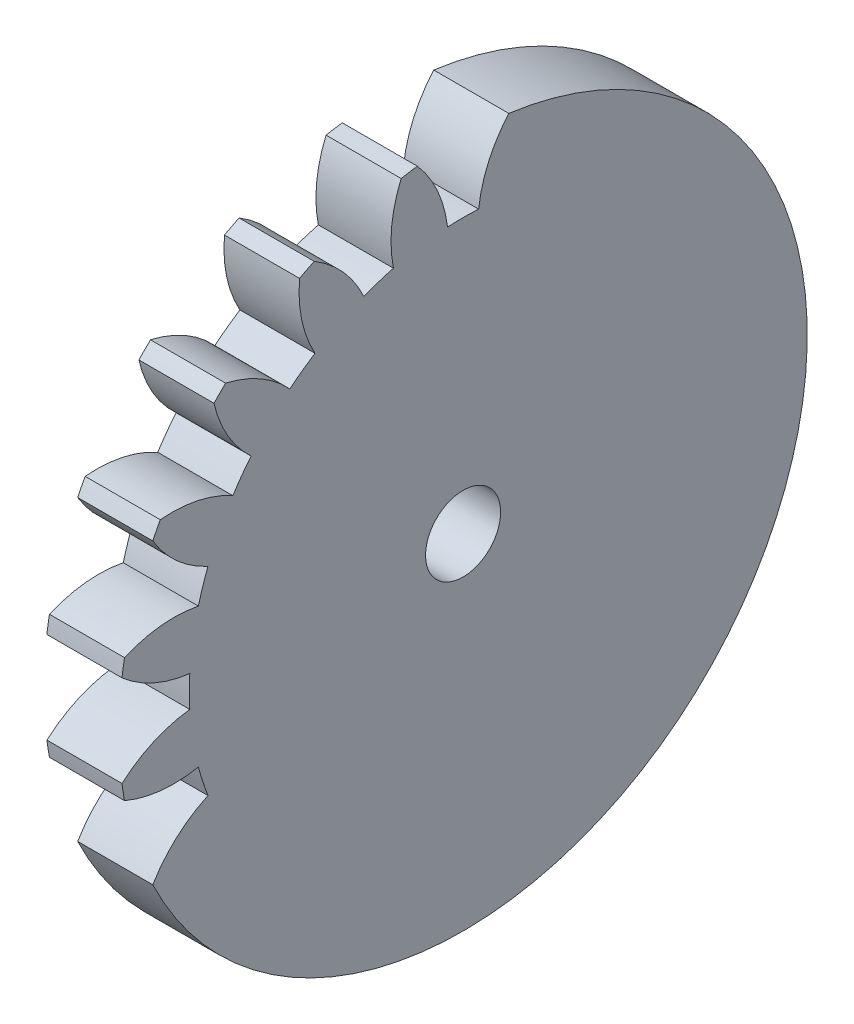
SolidWorks part; units mm, degrees
ref_plane "Plane1" through (0, 0, 0) normal (0, 0, 1) x (1, 0, 0)
ref_plane "Plane2" through (0, 0, 0) normal (0, 1, 0) x (1, 0, 0)
ref_plane "Plane3" through (0, 0, 0) normal (1, 0, 0) x (0, 0, -1)
sketch "HoldingSke" plane through (0, 0, 0) normal (0, 1, 0) x (1, 0, 0)
  line L0 (0, 0) -> (0.7518, -0.2736)
  line L1 (-15, 0) -> (100, 0) construction
  line L2 (0, 0) -> (-2.1039, 2.3779)
  line L3 (0, 0) -> (-11.863, 4.5341)
  line L4 (0, 0) -> (8.1152, 2.9537)
  line L5 (0, 0) -> (-46.8476, -17.4728)
  line L6 (0, 0) -> (-9.9476, -6.7116)
  line L7 (-2.1039, 2.3779) -> (8.6586, 51.2059)
  line L8 (-76.2, 54.61) -> (-75.7, 54.61)
  line L9 (-71.009, 38.7566) -> (-53.1078, 45.2721)
  line L10 (-76.2, 71.12) -> (104.1128, 71.12)
  line L11 (0, 0) -> (-12, 0)
  line L12 (-76.2, 101.6) -> (-76.155, 101.6)
  line L13 (24.9733, 27.94) -> (52.9518, 28.4284)
  line L14 (24.9733, 27.94) -> (24.9743, 27.94)
  line L15 (24.9733, 27.94) -> (100.4006, 29.5858)
  line L16 (-63.627, -1.25) -> (-12.827, -1.25)
  circle A0 centre (0, 0) radius 1.5
  circle A1 centre (0, 0) radius 10.9365
  circle A2 centre (0, 0) radius 37.5
  circle A3 centre (0, 0) radius 1.5
  dimension "Num_teeth" = 20
  dimension "Pitch_radius" = 180.3128
  dimension "Width" = 12
sketch "BasProSke" plane through (0, 0, 0) normal (0, 1, 0) x (1, 0, 0)
  line L0 (-10, 0) -> (60, 0) construction
  line L1 (0, 0) -> (0, 13.75)
  line L2 (0, 0) -> (3, 0)
  line L3 (3, 0) -> (3, 13.75)
  line L4 (3, 13.75) -> (0, 13.75)
  dimension "Thickness" = 3
  dimension "Diameter" = 27.5
revolve "Base-Revolve" add sketch "BasProSke" angle 360 about L0
sketch "TooCutSke" plane through (0, 0, 0) normal (1, 0, 0) x (0, 0, -1)
  line L1 (0, 0) -> (0, 107) construction
  line L2 (0, 0) -> (-1.0594, 12.455) construction
  line L3 (0, 0) -> (-3.9007, 24.6278) construction
  line L4 (-1.0594, 12.455) -> (-1.9503, 12.3139) construction
  arc A0 (0.6211, 10.9188) -> (-0.6211, 10.9188) centre (0, 0) ccw
  arc A1 (1.8466, 13.6511) -> (-1.8466, 13.6511) centre (0, 0) ccw
  circle A2 centre (0, 0) radius 12.5 construction
  circle A3 centre (0, 0) radius 11.7462 construction
  arc A4 (-0.6211, 10.9188) -> (-1.8466, 13.6511) centre (-5.5866, 10.3326) ccw
  arc A5 (1.8466, 13.6511) -> (0.6211, 10.9188) centre (5.5866, 10.3326) ccw
extrude "ToothCut" cut sketch "TooCutSke" along normal through all
fillet "Breaks" [suppressed] radius 0.025 tangent propagation no
fillet "RootFillets" [suppressed] radius 0.3135
pattern_circular "TeethCuts" count 7 every 18 about axis through (-10, 0, 0) along (1, 0, 0) of "ToothCut"
sketch "HubNeaOneSke" plane through (0, 0, 0) normal (-1, 0, 0) x (0, 0, 1)
  circle A0 centre (0, 0) radius 10.9365
  dimension "Diameter" = 21.873
extrude "HubNearOne" [suppressed] add sketch "HubNeaOneSke" along normal blind 47.0001
sketch "HubNeaBotSke" plane through (0, 0, 0) normal (-1, 0, 0) x (0, 0, 1)
  circle A0 centre (0, 0) radius 10.9365
  dimension "Diameter" = 21.873
extrude "HubNearBoth" [suppressed] add sketch "HubNeaBotSke" along normal blind 23.5
ref_plane "FarPln" through (3, 0, 0) normal (1, 0, 0) x (0, 0, -1)
sketch "HubFarSke" plane through (3, 0, 0) normal (1, 0, 0) x (0, 0, -1)
  circle A0 centre (0, 0) radius 10.9365
  dimension "Diameter" = 21.873
extrude "HubFar" [suppressed] add sketch "HubFarSke" along normal blind 23.5
sketch "BorSke" plane through (0, 0, 0) normal (1, 0, 0) x (0, 0, -1)
  circle A0 centre (0, 0) radius 1.5
  dimension "Diameter" = 3
extrude "Bore" cut sketch "BorSke" along normal mid plane 100.0001
sketch "KeySke" plane through (0, 0, 0) normal (1, 0, 0) x (0, 0, -1)
  line L0 (-0.6, 0) -> (-0.6, 2)
  line L1 (-0.6, 2) -> (0.6, 2)
  line L2 (0.6, 2) -> (0.6, 0)
  line L3 (0, 0) -> (0, 34) construction
  line L4 (-0.6, 0) -> (0.6, 0)
extrude "Keyway" [suppressed] cut sketch "KeySke" along normal mid plane 100.0001
equation "' \"Module@HoldingSke\" = 6.35"
equation "' \"Num_teeth@HoldingSke\" = 12"
equation "' \"Ap@HoldingSke\" =  20"
equation "' \"Ap@HoldingSke\" = 20"
equation "' \"Width@HoldingSke\" = 0.5 * 25.4"
equation "' \"Hub_dia@HoldingSke\"= 1 * 25.4"
equation "' \"Hub_dia@HoldingSke\" = 1 * 25.4"
equation "' \"Overall_len@HoldingSke\" = 1.0 * 25.4"
equation "' \"Bore@HoldingSke\" = 0.75 * 25.4"
equation "' \"T_dim@HoldingSke\" = 0.1 * 25.4"
equation "' \"Width@KeySke\" = 0.25 * 25.4"
equation "' \"Show_teeth@HoldingSke\" = 13"
equation "' \"Backlash@HoldingSke\" = 0.009 * 25.4"
equation "' \"Addendum_fac@HoldingSke\" = 1.0"
equation "' \"Dedendum_fac@HoldingSke\" = 1.25"
equation "' \"Dedendum_add@HoldingSke\" = 0.00005 * 25.4"
equation "' \"Clearance_fac@HoldingSke\" = 0.25"
equation "\"Pitch@HoldingSke\" = 1 / \"Module@HoldingSke\""
equation "\"Overcut_dia@TooCutSke\" = (\"Num_teeth@HoldingSke\" + 2 * \"Addendum_fac@HoldingSke\") / \"Pitch@HoldingSke\" + 0.002 * 25.4"
equation "\"Pitch_dia@TooCutSke\" = \"Num_teeth@HoldingSke\" / \"Pitch@HoldingSke\""
equation "\"Base_dia@TooCutSke\" = \"Num_teeth@HoldingSke\" / \"Pitch@HoldingSke\" * cos((\"Ap@HoldingSke\"  * 3.14159265 / 180))"
equation "\"Root_dia@TooCutSke\" = (\"Num_teeth@HoldingSke\" + 2) / \"Pitch@HoldingSke\" - 2 * (\"Addendum_fac@HoldingSke\" + \"Dedendum_fac@HoldingSke\") / \"Pitch@HoldingSke\" - \"Dedendum_add@HoldingSke\" * 2"
equation "\"Half_ang@TooCutSke\" = 180 / \"Num_teeth@HoldingSke\""
equation "\"Half_CT@TooCutSke\" = \"Num_teeth@HoldingSke\" / \"Pitch@HoldingSke\" * sin((3.14159265 / 2 / \"Num_teeth@HoldingSke\")) / 2 - 7 * \"Backlash@HoldingSke\" / 4"
equation "\"Flank_rad@TooCutSke\" = \"Num_teeth@HoldingSke\" / \"Pitch@HoldingSke\" / 5"
equation "\"Radius@RootFillets\" = \"Clearance_fac@HoldingSke\" / \"Pitch@HoldingSke\" + \"Dedendum_add@HoldingSke\""
equation "\"Break_rad@Breaks\" = 0.02 / \"Pitch@HoldingSke\""
equation "\"Thickness@HoldingSke\" = \"Width@HoldingSke\""
equation "\"OAL@HoldingSke\" = \"Thickness@HoldingSke\""
equation "\"MHD@HoldingSke\" = (\"Num_teeth@HoldingSke\" + 2) / \"Pitch@HoldingSke\" - 2 * (\"Addendum_fac@HoldingSke\" + \"Dedendum_fac@HoldingSke\")  / \"Pitch@HoldingSke\" - \"Dedendum_add@HoldingSke\" * 2"
equation "\"MBD@HoldingSke\" = (\"Num_teeth@HoldingSke\" + 2) / \"Pitch@HoldingSke\" - 2 * (\"Addendum_fac@HoldingSke\" + \"Dedendum_fac@HoldingSke\")  / \"Pitch@HoldingSke\" - \"Dedendum_add@HoldingSke\" * 2 - 0.002 * 25.4"
equation "\"MHD@HoldingSke\" = ((sgn( \"MHD@HoldingSke\" - \"Hub_dia@HoldingSke\" )-1)*( \"MHD@HoldingSke\" - \"Hub_dia@HoldingSke\" ))/-2+ \"Hub_dia@HoldingSke\""
equation "\"MBD@HoldingSke\" = ((sgn( \"MBD@HoldingSke\" - \"Bore@HoldingSke\" )-1)*( \"MBD@HoldingSke\" - \"Bore@HoldingSke\" ))/-2+ \"Bore@HoldingSke\""
equation "\"OAL@HoldingSke\" = ((sgn( \"OAL@HoldingSke\" - \"Overall_len@HoldingSke\" )+1)*( \"OAL@HoldingSke\" - \"Overall_len@HoldingSke\" ))/2 + \"Overall_len@HoldingSke\" + 0.000002 * 25.4"
equation "\"Num_teeth@TeethCuts\" = ((sgn( \"Num_teeth@TeethCuts\" - 2.0)+1)*( \"Num_teeth@TeethCuts\" - 2.0))/2 +2.0"
equation "\"Diameter@BasProSke\" = (\"Num_teeth@HoldingSke\" + 2 * \"Addendum_fac@HoldingSke\") / \"Pitch@HoldingSke\""
equation "' \"Fillet_rad@BasProSke\" =  \"Thickness@HoldingSke\" * 0.05"
equation "' \"Fillet_rad@BasProSke\" = \"Thickness@HoldingSke\" * 0.05"
equation "\"MHD@HoldingSke\" = ((sgn( \"MHD@HoldingSke\" - \"Root_dia@TooCutSke\" )-1)*( \"MHD@HoldingSke\" - \"Root_dia@TooCutSke\" ))/-2+ \"Root_dia@TooCutSke\""
equation "\"Diameter@HubNeaOneSke\" = \"MHD@HoldingSke\""
equation "\"Length@HubNearOne\" = \"OAL@HoldingSke\" - \"Thickness@BasProSke\""
equation "\"Diameter@HubNeaBotSke\" = \"MHD@HoldingSke\""
equation "\"Length@HubNearBoth\" = ( \"OAL@HoldingSke\" - \"Thickness@BasProSke\" ) / 2.0"
equation "\"Thickness@FarPln\" = \"Thickness@BasProSke\""
equation "\"Diameter@HubFarSke\" = \"MHD@HoldingSke\""
equation "\"Length@HubFar\" = ( \"OAL@HoldingSke\" - \"Thickness@BasProSke\" ) / 2.0"
equation "\"Diameter@BorSke\" = \"MBD@HoldingSke\""
equation "\"D1@Bore\" = \"OAL@HoldingSke\" * 2.0"
equation "\"D1@Keyway\" = \"OAL@HoldingSke\" * 2.0"
equation "\"Offset@KeySke\" = \"T_dim@HoldingSke\" + \"MBD@HoldingSke\" / 2.0"
